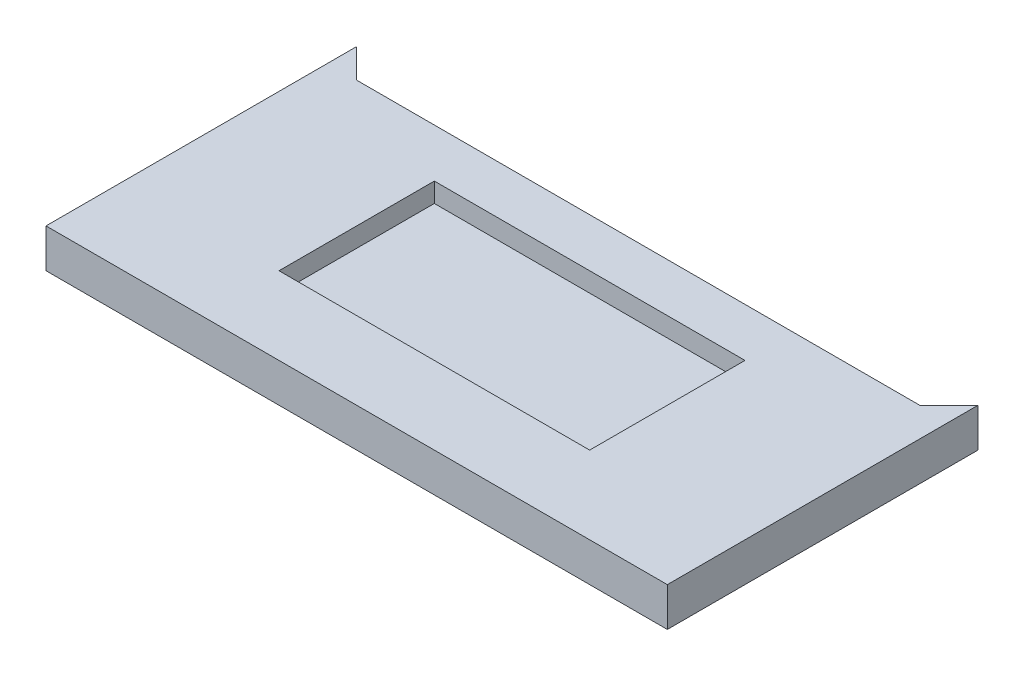
SolidWorks part; units mm, degrees
ref_plane "Спереди" through (0, 0, 0) normal (0, 0, 1) x (1, 0, 0)
ref_plane "Сверху" through (0, 0, 0) normal (0, 1, 0) x (1, 0, 0)
ref_plane "Сбоку" through (0, 0, 0) normal (1, 0, 0) x (0, 0, -1)
sketch "Эскиз1" plane through (0, 0, 0) normal (0, 1, 0) x (1, 0, 0)
  line L1 (-160, -80) -> (160, -80)
  line L2 (-160, -80) -> (-160, 80)
  line L3 (-160, 80) -> (160, 80)
  line L4 (160, -80) -> (160, 80)
  line L5 (-160, -80) -> (160, 80) construction
  line L6 (-160, 80) -> (160, -80) construction
  point P0 (0, 0)
  dimension "D1" = 160
  dimension "D2" = 320
extrude "Бобышка-Вытянуть1" add sketch "Эскиз1" along normal blind 20
sketch "Эскиз2" plane through (0, 20, 0) normal (0, 1, 0) x (1, 0, 0)
  line L1 (-80, -40) -> (80, -40)
  line L2 (-80, -40) -> (-80, 40)
  line L3 (-80, 40) -> (80, 40)
  line L4 (80, -40) -> (80, 40)
  line L5 (-80, -40) -> (80, 40) construction
  line L6 (-80, 40) -> (80, -40) construction
  point P0 (0, 0)
  dimension "D1" = 80
  dimension "D2" = 160
extrude "Вырез-Вытянуть1" cut sketch "Эскиз2" against normal blind 10
sketch "Эскиз3" plane through (0, 20, 0) normal (0, 1, 0) x (1, 0, 0)
  line L0 (-160, 80) -> (-145, 65)
  line L1 (-145, 65) -> (145, 65)
  line L2 (145, 65) -> (160, 80)
  line L3 (160, -80) -> (160, 80) construction
  line L4 (-160, 80) -> (-160, -80) construction
  line L5 (160, 80) -> (-160, 80) construction
  dimension "D1" = 45
  dimension "D2" = 45
  dimension "D3" = 15
extrude "Вырез-Вытянуть2" cut sketch "Эскиз3" against normal blind 20 and the other way through all
